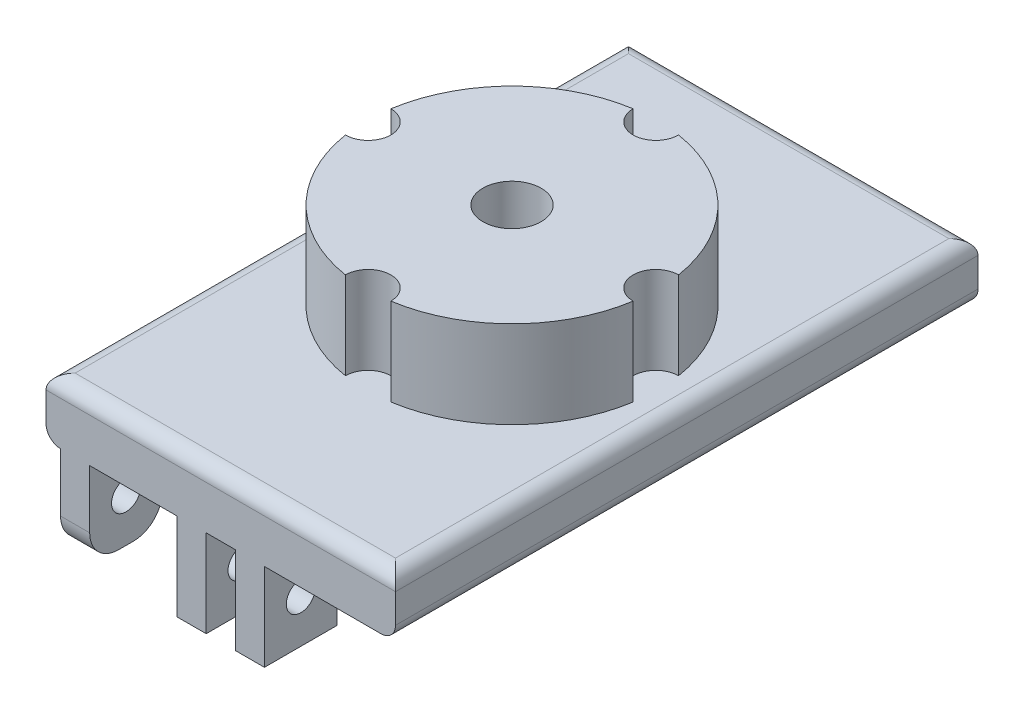
SolidWorks part; units mm, degrees
ref_plane "前视基准面" through (0, 0, 0) normal (0, 0, 1) x (1, 0, 0)
ref_plane "上视基准面" through (0, 0, 0) normal (0, 1, 0) x (1, 0, 0)
ref_plane "右视基准面" through (0, 0, 0) normal (1, 0, 0) x (0, 0, -1)
sketch "草图2" plane through (0, 0, 0) normal (0, 1, 0) x (1, 0, 0)
  line L1 (-60, 100) -> (60, 100)
  line L2 (-60, 100) -> (-60, -100)
  line L3 (-60, -100) -> (60, -100)
  line L4 (60, 100) -> (60, -100)
  line L5 (-60, 100) -> (60, -100) construction
  line L6 (-60, -100) -> (60, 100) construction
  point P0 (0, 0)
  dimension "D1" = 120
  dimension "D2" = 200
extrude "凸台-拉伸1" add sketch "草图2" along normal blind 20
sketch "草图3" plane through (0, 0, 0) normal (1, 0, 0) x (0, 0, -1)
  line L5 (100, 0) -> (92.0702, -19.8281)
  line L6 (100, 0) -> (79.999, 50.009)
  line L7 (67.9293, -19.8283) -> (59.999, 0)
  line L8 (79.999, 50.009) -> (59.999, 0)
  line L9 (100, 0) -> (-100, 0) construction
  line L10 (100, 0) -> (59.999, 0)
  line L11 (100, 0) -> (59.999, 0)
  arc A2 (92.0702, -19.8281) -> (67.9293, -19.8283) centre (79.9997, -15.0007) cw
  circle A3 centre (79.9997, -15.0007) radius 5
  dimension "D1" = 13
extrude "凸台-拉伸2" add sketch "草图3" against normal blind 10 from offset 7.5 contours A2 L5 L10 L7 A3 region at (0, -9.7327, -95.5817) offset against normal yes
sketch "草图4" plane through (0, 0, 0) normal (1, 0, 0) x (0, 0, -1)
  line L0 (-100, 0) -> (-75, 0)
  line L1 (-100, 0) -> (-100, -30)
  line L2 (-75, 0) -> (-75, -30)
  line L3 (-100, -30) -> (-75, -30)
  line L4 (100, 0) -> (-100, 0) construction
  circle A0 centre (-87.5, -15) radius 5
extrude "凸台-拉伸3" add sketch "草图4" along normal blind 10 from offset 5
mirror "镜向1" about plane through (0, 0, 0) normal (1, 0, 0) of "凸台-拉伸3"
extrude "凸台-拉伸4" add sketch "草图4<2>" against normal blind 10 from offset 45 offset against normal yes
sketch "草图4<2>" plane through (0, 0, 0) normal (1, 0, 0) x (0, 0, -1) same geometry as "草图4"
fillet "圆角2" radius 10 1 edges at (-50, -30, 100)
fillet "圆角3" radius 10 1 edges at (-50, -30, 75)
fillet "圆角4" radius 5 6 edges at (60, 0, 0) (-60, 0, 0) (0, 20, 100) (-60, 20, 0) (0, 20, -100) (60, 20, 0)
sketch "草图5" plane through (0, 20, 0) normal (0, 1, 0) x (1, 0, 0)
  line L0 (0, 0) -> (0, 54.6536) construction
  circle A0 centre (0, 0) radius 50
  arc A1 (-7.7936, 49.3889) -> (7.7936, 49.3889) centre (0, 49.3889) ccw
  arc A2 (49.3889, 7.7936) -> (49.3889, -7.7936) centre (49.3889, 0) ccw
  arc A3 (7.7936, -49.3889) -> (-7.7936, -49.3889) centre (0, -49.3889) ccw
  arc A4 (-49.3889, -7.7936) -> (-49.3889, 7.7936) centre (-49.3889, 0) ccw
  circle A5 centre (0, 0) radius 10
  point P4 (-7.7936, 49.3889)
  point P6 (7.7936, 49.3889)
  dimension "D1" = 4
extrude "凸台-拉伸5" add sketch "草图5" along normal blind 30 contours A4 A0 A3 A2 A1 region at (40.1983, 20, 0)
